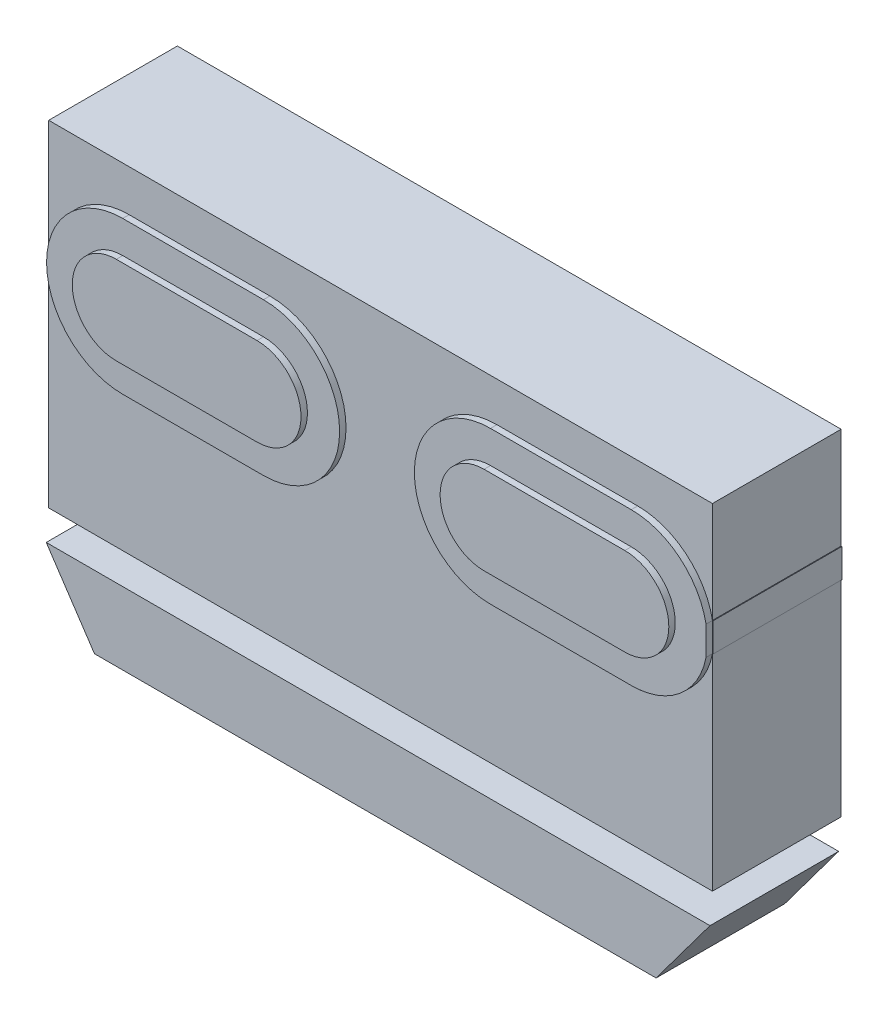
SolidWorks part; units mm, degrees
ref_plane "Front Plane" through (0, 0, 0) normal (0, 0, 1) x (1, 0, 0)
ref_plane "Top Plane" through (0, 0, 0) normal (0, 1, 0) x (1, 0, 0)
ref_plane "Right Plane" through (0, 0, 0) normal (1, 0, 0) x (0, 0, -1)
sketch "Sketch1" plane through (0, 0, 0) normal (0, 0, 1) x (1, 0, 0)
  line L0 (-64.2584, 9.2756) -> (-42.3751, 9.2756) construction
  line L1 (-76.7614, 27.5744) -> (26.4301, 27.5744)
  line L2 (-76.7614, 27.5744) -> (-76.7614, -24.6202)
  line L3 (-76.7614, -24.6202) -> (26.4301, -24.6202)
  line L4 (26.4301, 27.5744) -> (26.4301, -24.6202)
  line L5 (-64.2584, 16.1127) -> (-42.3751, 16.1127)
  line L6 (-64.2584, 2.4386) -> (-42.3751, 2.4386)
  line L7 (-7.0765, 9.5945) -> (14.8068, 9.5945) construction
  line L8 (-7.0765, 16.4315) -> (14.8068, 16.4315)
  line L9 (-7.0765, 2.7574) -> (14.8068, 2.7574)
  line L18 (-77.1454, -29.4533) -> (26.0461, -29.4533)
  line L19 (-77.1454, -29.4533) -> (26.0461, -29.4533)
  line L24 (26.0461, -29.4533) -> (17.6643, -40.6939)
  line L25 (-69.6457, -40.6939) -> (17.6643, -40.6939)
  line L26 (-77.1454, -29.4533) -> (-69.6457, -40.6939)
  line L27 (-64.2584, 21.1127) -> (-42.3751, 21.1127)
  line L28 (-64.2584, -2.5614) -> (-42.3751, -2.5614)
  line L29 (-7.0765, 21.4315) -> (14.8068, 21.4315)
  line L30 (-7.0765, -2.2426) -> (14.8068, -2.2426)
  arc A0 (-64.2584, 16.1127) -> (-64.2584, 2.4386) centre (-64.2584, 9.2756) ccw
  arc A1 (-42.3751, 2.4386) -> (-42.3751, 16.1127) centre (-42.3751, 9.2756) ccw
  arc A2 (-7.0765, 16.4315) -> (-7.0765, 2.7574) centre (-7.0765, 9.5945) ccw
  arc A3 (14.8068, 2.7574) -> (14.8068, 16.4315) centre (14.8068, 9.5945) ccw
  arc A4 (-42.3751, -2.5614) -> (-42.3751, 21.1127) centre (-42.3751, 9.2756) ccw
  arc A5 (-64.2584, 21.1127) -> (-64.2584, -2.5614) centre (-64.2584, 9.2756) ccw
  arc A6 (14.8068, -2.2426) -> (14.8068, 21.4315) centre (14.8068, 9.5945) ccw
  arc A7 (-7.0765, 21.4315) -> (-7.0765, -2.2426) centre (-7.0765, 9.5945) ccw
  point P6 (-53.3167, 9.2756)
  point P13 (3.8651, 9.5945)
  dimension "D1" = 5
  dimension "D2" = 5
extrude "Boss-Extrude2" add sketch "Sketch1" along normal blind 20 contours A7 L29 A6 L4 L1 L2 L3 L30 A5 L27 A4 L28 region at (-25.3991, -2.9165, 0)
extrude "Boss-Extrude3" add sketch "Sketch1<6>" along normal blind 20 separate body contours L18 L26 L25 L24 region at (-25.764, -34.9174, 0)
sketch "Sketch1<6>" plane through (0, 0, 0) normal (0, 0, 1) x (1, 0, 0) same geometry as "Sketch1"
sketch "Sketch2" plane through (26.4301, 0, 0) normal (1, 0, 0) x (0, 0, -1)
  line L1 (-20, 11.8336) -> (0, 11.8336)
  line L2 (-20, 11.8336) -> (-20, 7.3553)
  line L3 (-20, 7.3553) -> (0, 7.3553)
  line L4 (0, 11.8336) -> (0, 7.3553)
extrude "Boss-Extrude4" add sketch "Sketch2" along normal blind 0.1 separate body
extrude "Boss-Extrude6" add sketch "Sketch1<8>" along normal blind 21 contours L27 A5 L28 A4 A1 L6 A0 L5 | L6 A1 L5 A0 | L29 A7 L30 A6 L4 A3 L9 A2 L8 | L9 A3 L8 A2 region at (25.9186, 9.5945, 0) region at (-53.3167, 9.2756, 0) region at (3.8651, 9.5945, 0) region at (-53.3167, 20.5993, 0)
sketch "Sketch1<8>" plane through (0, 0, 0) normal (0, 0, 1) x (1, 0, 0) same geometry as "Sketch1"
extrude "Boss-Extrude7" add sketch "Sketch1<9>" along normal blind 22 contours L5 A1 L6 A0 | L8 A3 L9 A2
sketch "Sketch1<9>" plane through (0, 0, 0) normal (0, 0, 1) x (1, 0, 0) same geometry as "Sketch1"
